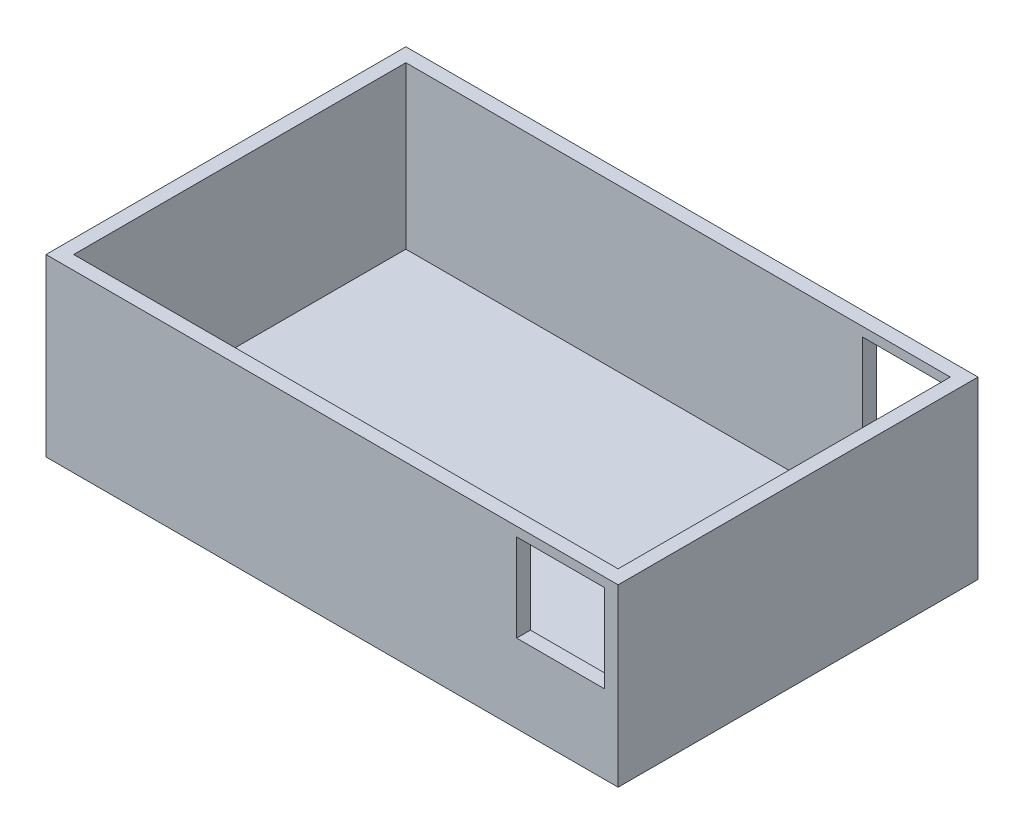
SolidWorks part; units mm, degrees
ref_plane "Front Plane" through (0, 0, 0) normal (0, 0, 1) x (1, 0, 0)
ref_plane "Top Plane" through (0, 0, 0) normal (0, 1, 0) x (1, 0, 0)
ref_plane "Right Plane" through (0, 0, 0) normal (1, 0, 0) x (0, 0, -1)
sketch "Sketch1" plane through (0, 0, 0) normal (0, 1, 0) x (1, 0, 0)
  line L1 (0, 0) -> (787.4, 0)
  line L2 (0, 0) -> (0, 495.3)
  line L3 (0, 495.3) -> (787.4, 495.3)
  line L4 (787.4, 0) -> (787.4, 495.3)
  dimension "D1" = 787.4
  dimension "D2" = 495.3
extrude "Boss-Extrude1" add sketch "Sketch1" along normal blind 241.3
shell "Shell1" thickness 19.05 removed face at (393.7, 241.3, -247.65)
sketch "Sketch2" plane through (0, 0, 0) normal (0, 0, 1) x (1, 0, 0)
  line L0 (787.4, 241.3) -> (787.4, 0) construction
  line L1 (768.35, 228.6) -> (647.7, 228.6)
  line L2 (768.35, 228.6) -> (768.35, 107.95)
  line L3 (768.35, 107.95) -> (647.7, 107.95)
  line L4 (647.7, 228.6) -> (647.7, 107.95)
  line L10 (0, 241.3) -> (787.4, 241.3) construction
  dimension "D1" = 120.65
  dimension "D2" = 120.65
  dimension "D3" = 19.05
  dimension "D4" = 12.7
extrude "Cut-Extrude1" cut sketch "Sketch2" against normal through all
